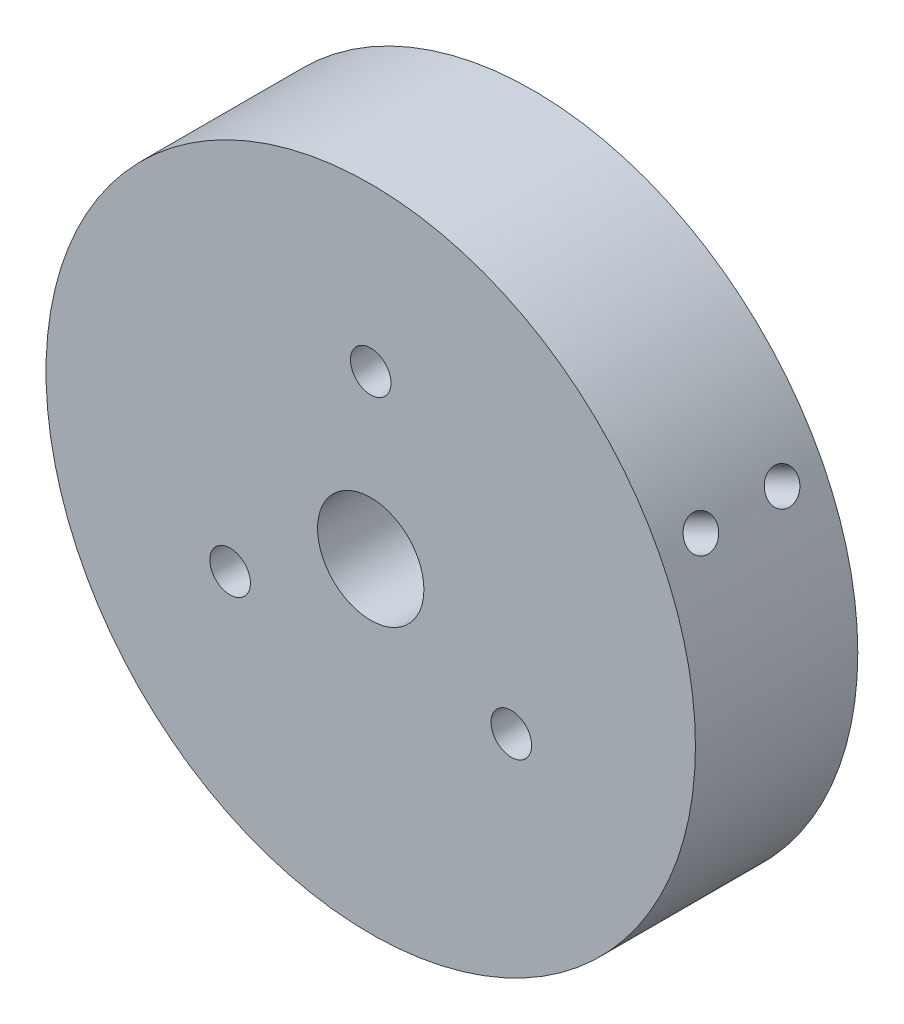
SolidWorks part; units mm, degrees
ref_plane "Front Plane" through (0, 0, 0) normal (0, 0, 1) x (1, 0, 0)
ref_plane "Top Plane" through (0, 0, 0) normal (0, 1, 0) x (1, 0, 0)
ref_plane "Right Plane" through (0, 0, 0) normal (1, 0, 0) x (0, 0, -1)
sketch "Sketch1" plane through (0, 0, 0) normal (0, 0, 1) x (1, 0, 0)
  circle A1 centre (0, 0) radius 20
  circle A6 centre (0, 0) radius 10 construction
  circle A7 centre (0, 10) radius 1.2505
  circle A8 centre (0, 0) radius 3.275
  circle A9 centre (8.6603, -5) radius 1.2505
  circle A10 centre (-8.6603, -5) radius 1.2505
  point P9 (0, 0)
  dimension "D1" = 20
  dimension "D2" = 40
  dimension "D3" = 6.55
  dimension "D4" = 2.501
  dimension "D5" = 3
extrude "Boss-Extrude1" add sketch "Sketch1" along normal blind 10
sketch "Sketch2" plane through (0, 0, 10) normal (0, 0, 1) x (1, 0, 0)
  line L0 (-1.2906, 1.9844) -> (1.2906, 1.9844) construction
  line L1 (-1.2906, 0) -> (1.2906, 0)
  line L2 (-1.2906, 0) -> (-1.2906, 4.6156)
  line L3 (-1.2906, 4.6156) -> (1.2906, 4.6156)
  line L4 (1.2906, 0) -> (1.2906, 4.6156)
  circle A0 centre (0, 0) radius 3.275 construction
  point P4 (0, 0)
  dimension "D1" = 2.5813
  dimension "D2" = 1.2906
  dimension "D3" = 2.6312
extrude "Cut-Extrude1" [suppressed] cut sketch "Sketch2" against normal through all both and the other way through all
sketch "Sketch3" plane through (0, 0, 10) normal (0, 0, 1) x (1, 0, 0)
  line L0 (-1.7653, 25.7548) -> (22.0432, -21.2285)
ref_plane "Plane1" through (8.9799, 4.5505, 0) normal (-0.892, -0.452, 0) x (0.452, -0.892, 0)
ref_axis "Axis1" through (0, 0, 10) along (0, 0, -1)
sketch "Sketch4" plane through (8.9799, 4.5505, 0) normal (-0.892, -0.452, 0) x (0.452, -0.892, 0)
  line L0 (-23.7715, 10) -> (28.9, 10) construction
  line L1 (0, 10) -> (0, 0) construction
  circle A0 centre (0, 7.5) radius 1
  circle A1 centre (0, 2.5) radius 1
  point P2 (0, 0)
  point P4 (0, 2.5489)
  dimension "D1" = 2
  dimension "D2" = 5
  dimension "D3" = 2.5
extrude "Cut-Extrude2" cut sketch "Sketch4" against normal up to next and the other way up to next
equation "\"D3@Sketch1\"=0.25in+0.2mm"
equation "\"D1@Sketch2\"=0.09375in+0.2mm"
equation "\"D2@Sketch2\"=0.046875in+0.1mm"
equation "\"D3@Sketch2\"=\"D1@Sketch2\"+0.05mm"
